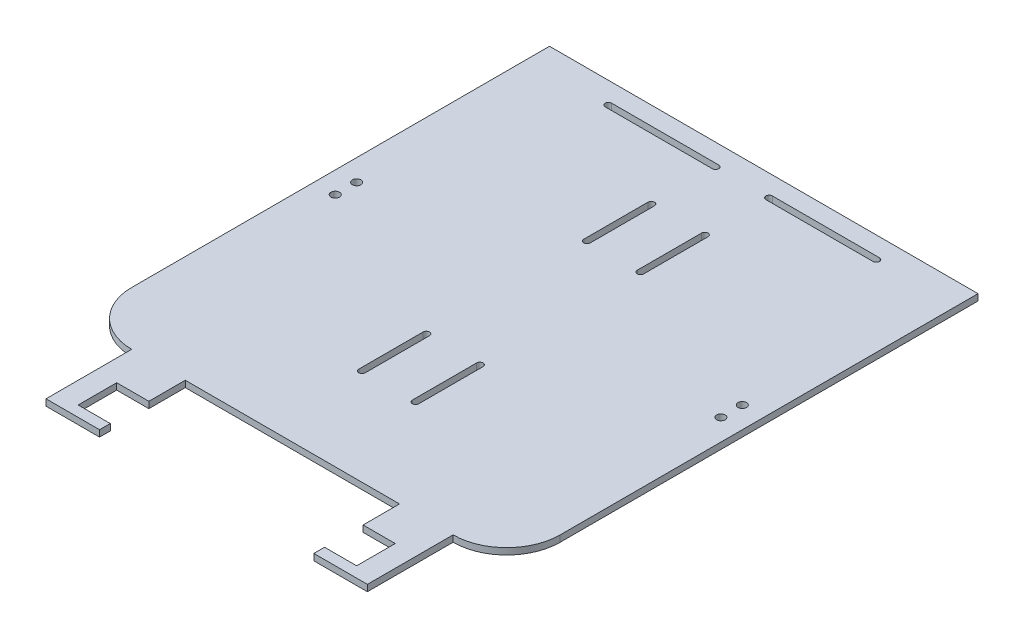
SolidWorks part; units mm, degrees
ref_plane "Front Plane" through (0, 0, 0) normal (0, 0, 1) x (1, 0, 0)
ref_plane "Top Plane" through (0, 0, 0) normal (0, 1, 0) x (1, 0, 0)
ref_plane "Right Plane" through (0, 0, 0) normal (1, 0, 0) x (0, 0, -1)
sketch "Sketch1" plane through (0, 0, 0) normal (0, 1, 0) x (1, 0, 0)
  line L0 (12.5, 210) -> (62.5, 210) construction
  line L1 (-75, 0) -> (75, 0)
  line L2 (0, 0) -> (0, 220) construction
  line L3 (-100, 220) -> (100, 220)
  line L4 (100, 25) -> (100, 220)
  line L5 (100, 200) -> (90, 200)
  line L6 (100, 200) -> (100, 135)
  line L7 (100, 135) -> (90, 135)
  line L8 (90, 200) -> (90, 135)
  line L9 (12.5, 211.5) -> (62.5, 211.5)
  line L10 (12.5, 208.5) -> (62.5, 208.5)
  line L11 (12.5, 180) -> (12.5, 150) construction
  line L12 (14, 180) -> (14, 150)
  line L13 (11, 180) -> (11, 150)
  line L14 (12.5, 75) -> (12.5, 45) construction
  line L15 (14, 75) -> (14, 45)
  line L16 (11, 75) -> (11, 45)
  line L17 (-90, 200) -> (-90, 135)
  line L18 (-100, 135) -> (-90, 135)
  line L19 (-100, 200) -> (-100, 135)
  line L20 (-100, 200) -> (-90, 200)
  line L21 (-100, 25) -> (-100, 220)
  line L22 (-12.5, 75) -> (-12.5, 45) construction
  line L23 (-14, 75) -> (-14, 45)
  line L24 (-11, 75) -> (-11, 45)
  line L25 (-12.5, 180) -> (-12.5, 150) construction
  line L26 (-14, 180) -> (-14, 150)
  line L27 (-11, 180) -> (-11, 150)
  line L28 (-12.5, 210) -> (-62.5, 210) construction
  line L29 (-12.5, 211.5) -> (-62.5, 211.5)
  line L30 (-12.5, 208.5) -> (-62.5, 208.5)
  line L31 (-50, -40) -> (-50, -35)
  line L32 (-75, 0) -> (-50, 0)
  line L33 (-75, 0) -> (-75, -40)
  line L34 (-75, -40) -> (-50, -40)
  line L35 (-50, 0) -> (-50, -40)
  line L36 (75, 0) -> (50, 0)
  line L37 (75, 0) -> (75, -40)
  line L38 (75, -40) -> (50, -40)
  line L39 (50, 0) -> (50, -40)
  line L40 (50, -40) -> (49.9323, -39.7896)
  line L41 (50, -40) -> (50, -35)
  line L43 (-50, -35) -> (-55, -35)
  line L44 (-50, -35) -> (-50, -17)
  line L45 (-50, -17) -> (-55, -17)
  line L46 (-55, -35) -> (-55, -17)
  line L47 (50, -35) -> (55, -35)
  line L48 (50, -35) -> (50, -17)
  line L49 (50, -17) -> (55, -17)
  line L50 (55, -35) -> (55, -17)
  arc A0 (12.5, 211.5) -> (12.5, 208.5) centre (12.5, 210) ccw
  arc A1 (62.5, 208.5) -> (62.5, 211.5) centre (62.5, 210) ccw
  circle A2 centre (90, 120) radius 2
  circle A3 centre (90, 110) radius 2
  arc A4 (14, 180) -> (11, 180) centre (12.5, 180) ccw
  arc A5 (11, 150) -> (14, 150) centre (12.5, 150) ccw
  arc A6 (75, 0) -> (100, 25) centre (75, 25) ccw
  arc A7 (14, 75) -> (11, 75) centre (12.5, 75) ccw
  arc A8 (11, 45) -> (14, 45) centre (12.5, 45) ccw
  arc A9 (-75, 0) -> (-100, 25) centre (-75, 25) cw
  circle A10 centre (-90, 110) radius 2
  circle A11 centre (-90, 120) radius 2
  arc A12 (-14, 75) -> (-11, 75) centre (-12.5, 75) cw
  arc A13 (-11, 45) -> (-14, 45) centre (-12.5, 45) cw
  arc A14 (-14, 180) -> (-11, 180) centre (-12.5, 180) cw
  arc A15 (-11, 150) -> (-14, 150) centre (-12.5, 150) cw
  arc A16 (-12.5, 211.5) -> (-12.5, 208.5) centre (-12.5, 210) cw
  arc A17 (-62.5, 208.5) -> (-62.5, 211.5) centre (-62.5, 210) cw
  point P11 (37.5, 210)
  point P22 (12.5, 165)
  point P29 (100, 0)
  point P32 (12.5, 60)
  point P51 (-12.5, 60)
  point P56 (-100, 0)
  point P59 (-12.5, 165)
  point P66 (-37.5, 210)
  dimension "D9" = 10
  dimension "D11" = 4
  dimension "D14" = 4
  dimension "D19" = 25
  dimension "D23" = 1.5
  dimension "D1" = 100
  dimension "D2" = 220
  dimension "D3" = 65
  dimension "D4" = 10
  dimension "D5" = 50
  dimension "D6" = 37.5
  dimension "D7" = 3
  dimension "D8" = 10
  dimension "D10" = 100
  dimension "D12" = 10
  dimension "D13" = 10
  dimension "D15" = 3
  dimension "D16" = 30
  dimension "D17" = 20
  dimension "D18" = 55
  dimension "D20" = 3
  dimension "D21" = 30
  dimension "D22" = 12.5
  dimension "D24" = 60
  dimension "D25" = 25
  dimension "D26" = 25
  dimension "D27" = 40
  dimension "D28" = 40
  dimension "D29" = 5
  dimension "D30" = 18
  dimension "D31" = 18
  dimension "D32" = 5
  dimension "D33" = 5
extrude "Boss-Extrude1" add sketch "Sketch1" along normal blind 3 contours A9 L1 A6 L4 L7 L8 L5 L3 L21 L20 L17 L18 L27 A15 L26 A14 A11 A1 L10 A0 L9 A2 A3 A5 L13 A4 L12 A8 L16 A7 L15 A10 L24 A13 L23 A12 L30 A17 L29 region at (0, 0, -108.0955)
sketch "Sketch2" plane through (0, 3, 0) normal (0, 1, 0) x (1, 0, 0)
  line L0 (-100, 25) -> (-100, 135) construction
  line L1 (90, 200) -> (90, 135) construction
  line L2 (-75, 0) -> (75, 0) construction
  line L3 (-90, 200) -> (-90, 135) construction
  line L4 (-100, 220) -> (100, 220) construction
  circle A0 centre (-80, 20) radius 3
  circle A1 centre (30, 20) radius 3
  circle A2 centre (-80, 180) radius 3
  circle A3 centre (80, 180) radius 3
  dimension "D5" = 6
  dimension "D6" = 6
  dimension "D7" = 6
  dimension "D10" = 6
  dimension "D1" = 20
  dimension "D2" = 20
  dimension "D3" = 110
  dimension "D4" = 20
  dimension "D8" = 10
  dimension "D9" = 40
  dimension "D11" = 10
  dimension "D12" = 40
sketch "Sketch3" plane through (0, 0, 0) normal (0, 1, 0) x (1, 0, 0)
  line L0 (100, 25) -> (100, 135) construction
  line L1 (-75, 0) -> (75, 0) construction
  circle A0 centre (-18.4, 50) radius 3.8
  circle A1 centre (68.4, 50) radius 3.8
  dimension "D1" = 86.8
  dimension "D4" = 7.6
  dimension "D5" = 7.6
  dimension "D2" = 31.6
  dimension "D3" = 50
  dimension "D6" = 50
extrude "Boss-Extrude4" add sketch "Sketch1<3>" along normal blind 3 contours L33 L34 L35 L32 | L36 L39 L38 L37
sketch "Sketch1<3>" plane through (0, 0, 0) normal (0, 1, 0) x (1, 0, 0) same geometry as "Sketch1"
sketch "Sketch4" plane through (0, 3, 0) normal (0, 1, 0) x (1, 0, 0)
  line L0 (-50, -40) -> (-50, -35)
  line L1 (-50, 0) -> (-50, -40) construction
  line L2 (50, -40) -> (50, -35)
  line L3 (50, 0) -> (50, -40) construction
  line L5 (-50, -35) -> (-55, -35)
  line L6 (-50, -35) -> (-50, -17)
  line L7 (-50, -17) -> (-55, -17)
  line L8 (-55, -35) -> (-55, -17)
  line L9 (50, -35) -> (55, -35)
  line L10 (50, -35) -> (50, -17)
  line L11 (50, -17) -> (55, -17)
  line L12 (55, -35) -> (55, -17)
  dimension "D1" = 5
  dimension "D2" = 5
  dimension "D3" = 18
  dimension "D4" = 5
  dimension "D5" = 5
  dimension "D6" = 18
extrude "Cut-Extrude1" cut sketch "Sketch4" against normal blind 10 contours L8 L5 L6 L7 | L9 L12 L11 L10 region at (-52.5, 3, 26) region at (52.5, 3, 26)
sketch "Sketch5" plane through (0, 3, 0) normal (0, 1, 0) x (1, 0, 0)
  line L1 (55, -35) -> (65, -35)
  line L2 (55, -35) -> (55, -17)
  line L3 (55, -17) -> (65, -17)
  line L4 (65, -35) -> (65, -17)
  dimension "D1" = 10
  dimension "D2" = 18
sketch "Sketch8" plane through (0, 3, 0) normal (0, 1, 0) x (1, 0, 0)
  line L1 (-55, -35) -> (-65, -35)
  line L2 (-55, -35) -> (-55, -17)
  line L3 (-55, -17) -> (-65, -17)
  line L4 (-65, -35) -> (-65, -17)
  dimension "D1" = 10
  dimension "D2" = 18
extrude "Cut-Extrude2" cut sketch "Sketch5" against normal blind 10
extrude "Cut-Extrude3" cut sketch "Sketch8" against normal blind 10
sketch "Sketch9" plane through (0, 3, 0) normal (0, 1, 0) x (1, 0, 0)
  line L1 (-90, 200) -> (-100, 200)
  line L2 (-90, 200) -> (-90, 135)
  line L3 (-90, 135) -> (-100, 135)
  line L4 (-100, 200) -> (-100, 135)
  line L5 (90, 200) -> (100, 200)
  line L6 (90, 200) -> (90, 135)
  line L7 (90, 135) -> (100, 135)
  line L8 (100, 200) -> (100, 135)
extrude "Boss-Extrude7" add sketch "Sketch9" against normal blind 3
